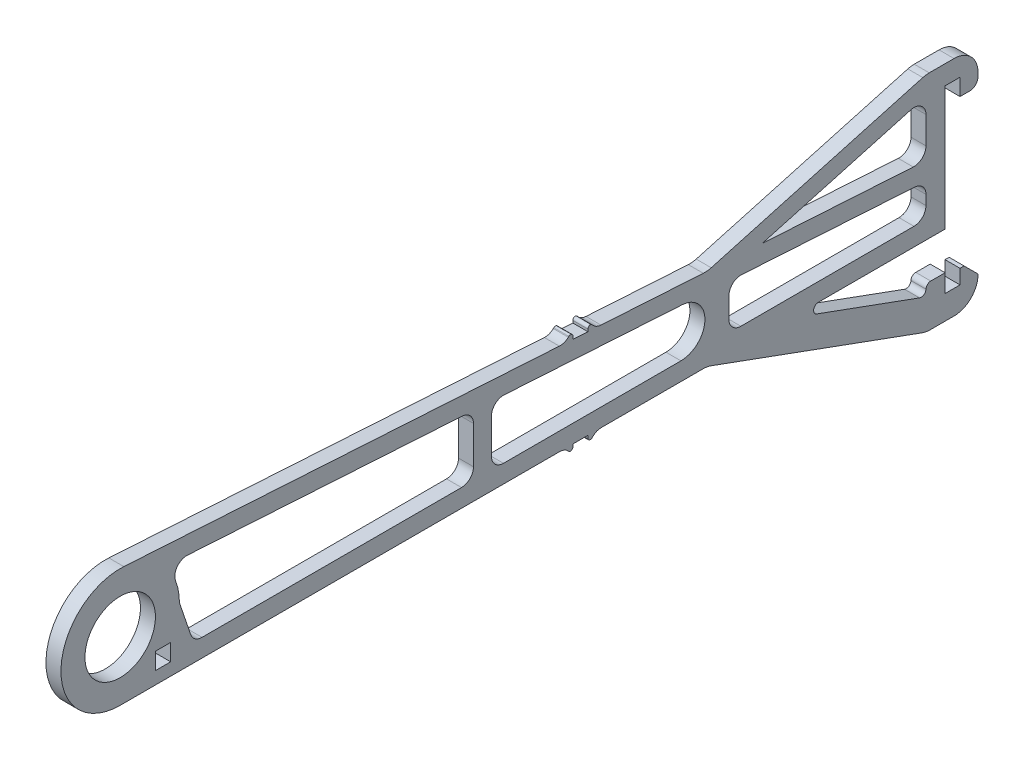
SolidWorks part; units mm, degrees
material "Delrin"
ref_plane "Front Plane" through (0, 0, 0) normal (0, 0, 1) x (1, 0, 0)
ref_plane "Top Plane" through (0, 0, 0) normal (0, 1, 0) x (1, 0, 0)
ref_plane "Right Plane" through (0, 0, 0) normal (1, 0, 0) x (0, 0, -1)
sketch "Sketch1" plane through (0, 0, 0) normal (1, 0, 0) x (0, 0, -1)
  line L0 (0.3859, 6.2619) -> (62.1851, 2.453)
  line L1 (0, -6.2738) -> (62.1851, -6.2738)
  line L2 (85.344, 8.8996) -> (88.3158, 8.8996)
  line L3 (4.7629, 4.0835) -> (85.344, -0.883)
  line L4 (4.5027, -4.3688) -> (85.344, -4.3688)
  line L5 (4.101, 4.1243) -> (87.7175, -1.0293) construction
  line L6 (0, -4.3688) -> (85.344, -4.3688) construction
  line L7 (85.344, -6.2738) -> (85.344, 8.8996) construction
  line L16 (6.2738, 0) -> (7.7597, -4.3688)
  line L17 (39.3251, 1.9533) -> (39.3251, -4.3688)
  line L18 (37.4201, 2.0707) -> (37.4201, -4.3688)
  line L23 (4.2182, 6.0257) -> (87.8347, 0.8721) construction
  line L24 (89.9668, 5.0896) -> (88.9508, 5.0896)
  line L25 (88.9508, 5.0896) -> (88.9508, 6.8676)
  line L26 (88.9508, 6.8676) -> (87.376, 6.8676)
  line L27 (87.376, 6.8676) -> (87.376, -6.2738)
  line L28 (87.376, -12.1824) -> (88.9508, -12.1824)
  line L29 (88.9508, -12.1824) -> (88.9508, -10.6584)
  line L30 (88.9508, -10.6584) -> (89.3826, -10.6584)
  line L31 (90.8558, -12.1316) -> (90.8558, -12.1824)
  line L32 (88.3158, -14.7224) -> (85.344, -14.7224)
  line L33 (85.344, -14.7224) -> (85.344, -6.2738) construction
  line L34 (90.8558, 5.9786) -> (90.8558, 6.3596)
  line L35 (89.3826, -10.6584) -> (90.8558, -12.1316)
  line L36 (64.4711, 0.4035) -> (64.4711, -4.3688)
  line L37 (62.1851, 0.5444) -> (62.1851, -4.3688)
  line L38 (62.1851, 2.453) -> (85.344, 8.8996)
  line L39 (68.0011, 2.0945) -> (85.344, 6.9222)
  line L40 (62.1851, -6.2738) -> (85.344, -14.7224)
  line L41 (71.0788, -6.2738) -> (85.344, -11.4779)
  line L42 (63.2297, -3.4104) -> (86.3886, -11.859) construction
  line L43 (62.696, 0.6178) -> (85.8549, 7.0644) construction
  line L44 (71.0788, -6.2738) -> (85.344, -6.2738)
  line L45 (0, -6.2738) -> (85.344, -6.2738) construction
  line L46 (68.0011, 2.0945) -> (85.344, 1.0256)
  line L47 (62.1851, -4.3688) -> (62.1851, 49995.6312) construction
  line L48 (85.344, 6.9222) -> (85.344, 1.0256)
  line L49 (85.344, -0.883) -> (85.344, -4.3688)
  line L50 (87.376, -12.1824) -> (87.376, -10.2774)
  line L51 (85.344, -6.2738) -> (87.376, -6.2738)
  line L52 (87.376, -10.2774) -> (85.344, -10.2774)
  line L53 (85.344, -10.2774) -> (85.344, -11.4779)
  circle A0 centre (0, 0) radius 3.7338
  circle A1 centre (0, 0) radius 6.2738
  arc A2 (88.3158, 8.8996) -> (90.8558, 6.3596) centre (88.3158, 6.3596) cw
  arc A3 (90.8558, -12.1824) -> (88.3158, -14.7224) centre (88.3158, -12.1824) cw
  arc A4 (90.8558, 5.9786) -> (89.9668, 5.0896) centre (89.9668, 5.9786) cw
  point P47 (90.8558, 8.8996)
  point P50 (90.8558, -14.7224)
  point P53 (90.8558, 5.0896)
  point P54 (90.8558, -10.6584)
  point P56 (90.8558, -10.6584)
  dimension "D1" = 7.4676
  dimension "D2" = 2.54
  dimension "D3" = 5.842
  dimension "D8" = 1.5748
  dimension "D18" = 2.54
  dimension "D19" = 2.54
  dimension "D20" = 0.889
  dimension "D21" = 22.86
  dimension "D5" = 37.4201
  dimension "D10" = 1.905
  dimension "D11" = 1.778
  dimension "D12" = 1.905
  dimension "D4" = 5.3842
  dimension "D9" = 1.5748
  dimension "D14" = 1.524
  dimension "D15" = 3.81
  dimension "D16" = 4.064
  dimension "D17" = 1.905
  dimension "D22" = 19.05
  dimension "D23" = 85.344
  dimension "D24" = 2.032
  dimension "D25" = 2.286
  dimension "D29" = 1.905
  dimension "D6" = 1.905
  dimension "D7" = 1.905
  dimension "D27" = 3.048
  dimension "D28" = 1.905
extrude "Boss-Extrude1" add sketch "Sketch1" along normal blind 1.5875 contours A1 L1 | A1 L4 L16 | L3 L18 L4 L17 | L31 L30 L29 L28 L27 L26 L25 L24 A4 L34 A2 L2 L7 L33 L32 A3 | A1 A0 | L3 L37 L4 L36 region at (0, 3.4205, -31.2278) region at (0, 5.4578, -2.7163) region at (0, -1.1783, -38.3697) region at (0, -3.082, -6.3381) region at (0, -1.9473, -63.3226)
fillet "Fillet1" radius 2.54 4 edges at (0.7937, 2.453, -62.1851) (0.7937, 8.8996, -85.344) (0.7937, -6.2738, -62.1851) (0.7937, -14.7224, -85.344)
fillet "Fillet2" radius 1.27 12 edges at (0.7937, 4.0835, -4.7629) (0.7937, -4.3688, -7.7597) (0.7937, -4.3688, -37.4201) (0.7937, 2.0707, -37.4201) (0.7937, -4.3688, -39.3251) (0.7937, 1.9533, -39.3251) (0.7937, 0.4035, -64.4711) (0.7937, -4.3688, -64.4711) (0.7937, 1.0256, -85.344) (0.7937, 6.9222, -85.344) (0.7937, -0.883, -85.344) (0.7937, -4.3688, -85.344)
fillet "Fillet3" radius 0.508 2 edges at (0.7937, -6.2738, -71.0788) (0.7937, -11.4779, -85.344)
fillet "Fillet4" radius 0.508 1 edges at (0.7937, -10.2774, -85.344)
sketch "Sketch4" plane through (1.5875, 0, 0) normal (1, 0, 0) x (0, 0, -1)
  line L0 (40.6732, 1.8702) -> (62.1851, 0.5444) construction
  line L1 (62.1851, 0.5444) -> (62.1851, -4.3688) construction
  line L2 (40.5951, -4.3688) -> (62.1851, -4.3688) construction
  line L3 (59.5471, 0.707) -> (62.1851, 0.5444)
  line L4 (62.1851, 0.5444) -> (62.1851, -4.3688)
  line L5 (59.3908, -4.3688) -> (62.1851, -4.3688)
  line L6 (61.9311, -1.8285) -> (62.1851, -1.8285) construction
  line L7 (87.376, 6.8676) -> (87.376, -6.2738) construction
  line L8 (40.5951, -4.3688) -> (62.1851, -4.3688) construction
  arc A0 (59.5471, 0.707) -> (59.3908, -4.3688) centre (59.3908, -1.8285) cw
  dimension "D1" = 0.254
extrude "Boss-Extrude2" add sketch "Sketch4" against normal up to surface (1.5875 mm away) up to face at (0, -0.6692, -20.2932)
sketch "Sketch5" plane through (1.5875, 0, 0) normal (1, 0, 0) x (0, 0, -1)
  line L4 (3.7592, -3.175) -> (3.7592, -4.953)
  line L5 (3.7592, -4.953) -> (5.3467, -4.953)
  line L6 (5.3467, -4.953) -> (5.3467, -3.175)
  line L7 (5.3467, -3.175) -> (3.7592, -3.175)
  line L8 (3.7592, -3.175) -> (3.7592, -4.953)
  line L9 (3.7592, -4.953) -> (5.3467, -4.953)
  line L10 (5.3467, -4.953) -> (5.3467, -3.175)
  line L11 (5.3467, -3.175) -> (3.7592, -3.175)
  dimension "D1" = 0
extrude "Cut-Extrude1" cut sketch "Sketch5" against normal up to next
sketch "Sketch6" plane through (0, 0, 0) normal (-1, 0, 0) x (0, 0, 1)
  line L0 (-47.0577, -6.2738) -> (-47.9467, -7.1628)
  line L1 (0, -6.2738) -> (-61.7363, -6.2738) construction
  line L2 (-47.9467, -17.1193) -> (-47.9467, 10.2613) construction
  line L3 (-47.9467, -7.1628) -> (-47.9467, -6.2738)
  line L4 (-47.9467, -6.2738) -> (-47.0577, -6.2738)
  line L5 (-47.0577, -6.2738) -> (-47.0715, -6.2496)
  line L6 (-48.7404, -10.0838) -> (-48.7404, 6.4573) construction
  line L7 (-49.5342, -10.0838) -> (-47.9467, -10.0838) construction
  line L8 (-49.5342, -6.2738) -> (-50.4232, -6.2738)
  line L9 (-49.5342, -7.1628) -> (-49.5342, -6.2738)
  line L10 (-50.4232, -6.2738) -> (-49.5342, -7.1628)
  line L11 (-50.4215, 3.178) -> (-49.5342, 4.1217)
  line L12 (-0.3859, 6.2619) -> (-61.759, 2.4793) construction
  line L13 (-49.5342, -17.1193) -> (-49.5342, 10.2613) construction
  line L14 (-49.5342, 4.1217) -> (-49.5342, 3.2327)
  line L15 (-49.5342, 3.2327) -> (-50.4215, 3.178)
  line L16 (-47.9467, 3.3306) -> (-47.0594, 3.3853)
  line L17 (-47.0594, 3.3853) -> (-47.9467, 4.2196)
  line L18 (-47.9467, 4.2196) -> (-47.9467, 3.3306)
  dimension "D1" = 0.889
extrude "Boss-Extrude3" add sketch "Sketch6" against normal up to surface (1.5875 mm away) contours L4 L3 L0 | L8 L10 L9 | L15 L14 L11 | L17 L18 L16 region at (0, -6.5701, -47.6504) region at (0, -6.5701, -49.8305) region at (0, 3.5108, -49.83) region at (0, 3.6451, -47.6509) up to face at (1.5875, -4.064, -4.553)
fillet "Fillet5" radius 1.27 4 edges at (0.7937, 3.178, -50.4215) (0.7937, 3.3853, -47.0594) (0.7937, -6.2738, -50.4232) (0.7937, -6.2738, -47.0577)
fillet "Fillet6" radius 0.254 4 edges at (0.7937, -7.1628, -49.5342) (0.7937, -7.1628, -47.9467) (0.7937, 4.2196, -47.9467) (0.7937, 4.1217, -49.5342)
